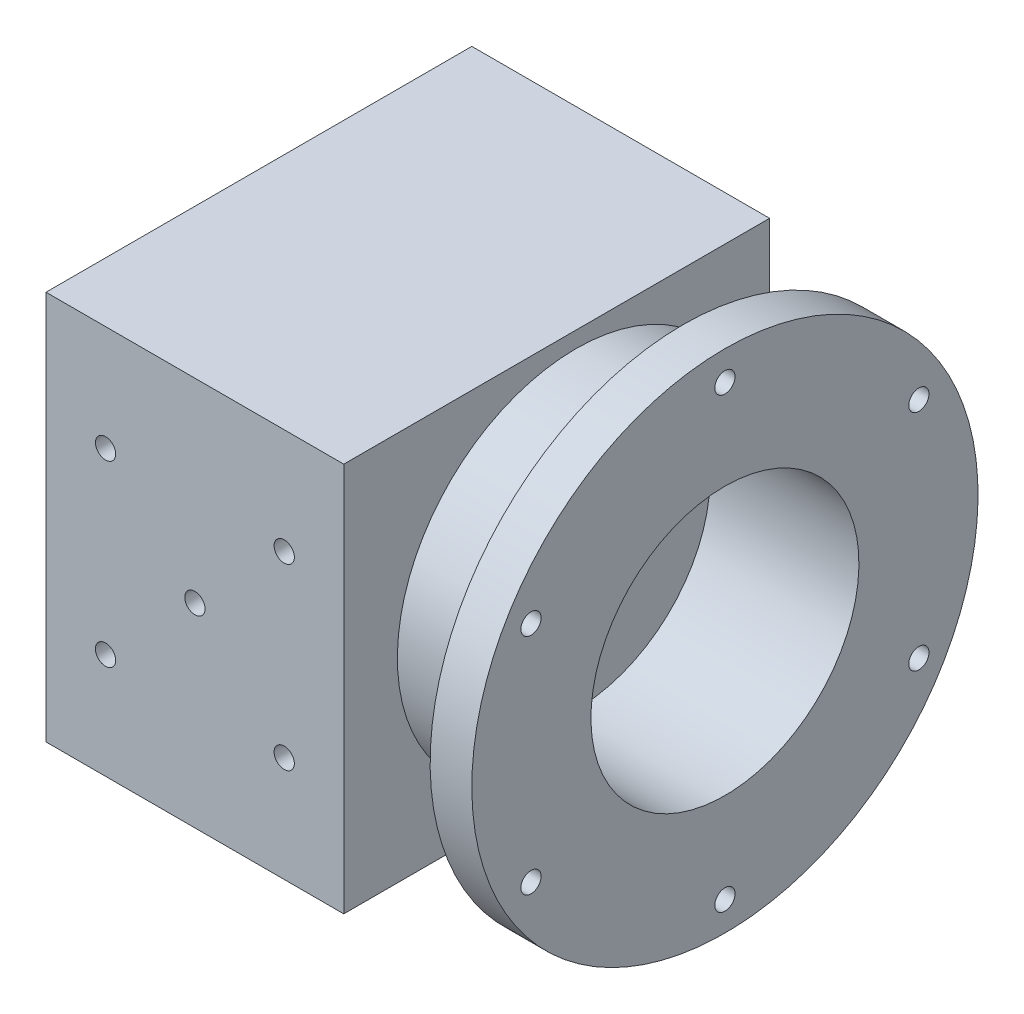
SolidWorks part; units mm, degrees
other "Elemento de detalle1"
other "Carpeta de soldadura"
other "Cordón de soldadura1"
material "6063-T5"
ref_plane "Front" through (0, 0, 0) normal (0, 0, 1) x (1, 0, 0)
ref_plane "Top" through (0, 0, 0) normal (0, 1, 0) x (1, 0, 0)
ref_plane "Right" through (0, 0, 0) normal (1, 0, 0) x (0, 0, -1)
sketch "Croquis1" plane through (0, 0, 0) normal (0, 0, 1) x (1, 0, 0)
  line L0 (55, 0) -> (-55, 0) construction
  line L1 (-25, 32.7) -> (25, 32.7)
  line L2 (25, 32.7) -> (25, -32.7)
  line L3 (25, -32.7) -> (-25, -32.7)
  line L4 (0, -55) -> (0, 55) construction
  line L5 (-25, 32.7) -> (-25, -32.7)
  point P8 (25, 0)
  point P12 (0, -32.7)
  dimension "D1" = 50
  dimension "D2" = 65.4
extrude "Saliente-Extruir1" add sketch "Croquis1" along normal mid plane 71.5
sketch "Croquis2" plane through (25, 0, 0) normal (1, 0, 0) x (0, 0, -1)
  line L0 (27.5, 0) -> (-27.5, 0) construction
  line L1 (0, 27.5) -> (0, -27.5) construction
  circle A0 centre (3.25, 0) radius 30
  circle A1 centre (3.25, 0) radius 22.5
  dimension "D1" = 60
  dimension "D2" = 45
  dimension "D3" = 3.25
extrude "Saliente-Extruir2" add sketch "Croquis2" along normal blind 25 separate body
sketch "Croquis3" plane through (50, 0, 0) normal (1, 0, 0) x (0, 0, -1)
  circle A0 centre (3.25, 0) radius 42.5
  circle A1 centre (3.25, 0) radius 30 construction
  circle A2 centre (3.25, 0) radius 30
  dimension "D1" = 85
extrude "Saliente-Extruir3" add sketch "Croquis3" against normal blind 7
hole_wizard "Taladro de margen para M31" positions "Croquis4" profile "Croquis5" hole size "M3" standard "Ansi Metric" end condition up to next
sketch "Croquis4" plane through (50, 0, 0) normal (1, 0, 0) x (0, 0, -1)
  line L0 (0, 42.3756) -> (0, 32.7) construction
  line L1 (0, 41.25) -> (0, -41.25) construction
  line L2 (0, 0) -> (3.25, 0) construction
  line L5 (41.25, 0) -> (-41.25, 0) construction
  circle A1 centre (3.25, 0) radius 42.5 construction
  point P15 (3.25, 37.6)
  point P22 (35.8126, 18.8)
  point P23 (35.8126, -18.8)
  point P24 (3.25, -37.6)
  point P25 (-29.3126, -18.8)
  point P26 (-29.3126, 18.8)
  dimension "D1" = 37.6
  dimension "D3" = 37.6
  dimension "D2" = 6
sketch "Croquis5" plane through (50, 18.8, 29.3126) normal (0, 1, 0) x (0, 0, -1)
  line L0 (0, 0) -> (0, 7.001)
  line L1 (0, 7.001) -> (1.7, 7.001)
  line L2 (1.7, 7.001) -> (1.7, 0)
  line L5 (1.7, 0) -> (0, 0)
  line L11 (0, -6.35) -> (0, 107.95) construction
  dimension "Diámetro de taladro hasta el siguiente" = 3.4
  dimension "Profundidad de taladro hasta el siguiente" = 7.001
hole_wizard "Taladro de margen para M32" positions "Croquis10" profile "Croquis12" hole size "M3" standard "Ansi Metric" end condition through all
sketch "Croquis10" plane through (0, 0, 35.75) normal (0, 0, 1) x (1, 0, 0)
  line L1 (-15, -15) -> (15, -15) construction
  line L2 (-15, -15) -> (-15, 15) construction
  line L3 (-15, 15) -> (15, 15) construction
  line L4 (15, -15) -> (15, 15) construction
  line L5 (-15, -15) -> (15, 15) construction
  line L6 (-15, 15) -> (15, -15) construction
  point P2 (15, 15)
  point P17 (-15, -15)
  point P18 (-15, 15)
  point P19 (15, -15)
  point P32 (0, 0)
  dimension "D1" = 30
sketch "Croquis12" plane through (15, 15, 35.75) normal (1, 0, 0) x (0, -1, 0)
  line L0 (0, 0) -> (0, 81.5)
  line L1 (0, 81.5) -> (1.7, 81.5)
  line L2 (1.7, 81.5) -> (1.7, 0)
  line L5 (1.7, 0) -> (0, 0)
  line L11 (0, -6.35) -> (0, 107.95) construction
  dimension "Diámetro de taladro hasta el siguiente" = 3.4
  dimension "Profundidad de taladro hasta el siguiente" = 81.5
sketch "Croquis14" plane through (0, 0, 0) normal (0, 1, 0) x (1, 0, 0)
  line L0 (50, 3.25) -> (-75, 3.25) construction
  line L1 (-75, 3.25) -> (-75, -6.4651) construction
  line L3 (50, -39.25) -> (50, 45.75) construction
  line L4 (-25, -35.75) -> (-25, 35.75) construction
  dimension "D1" = 50
